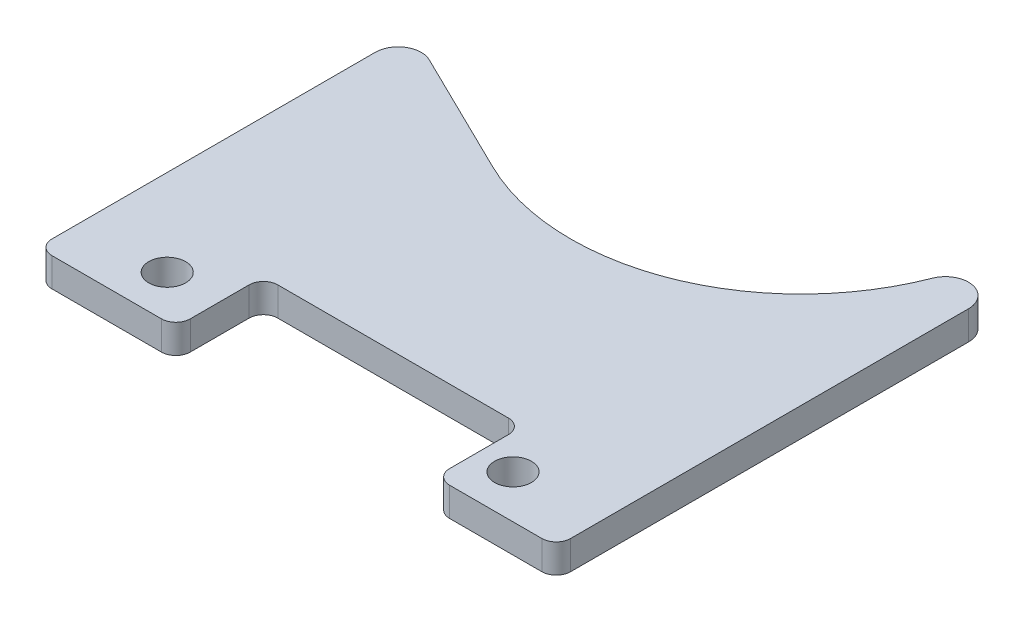
SolidWorks part; units mm, degrees
ref_plane "Front Plane" through (0, 0, 0) normal (0, 0, 1) x (1, 0, 0)
ref_plane "Top Plane" through (0, 0, 0) normal (0, 1, 0) x (1, 0, 0)
ref_plane "Right Plane" through (0, 0, 0) normal (1, 0, 0) x (0, 0, -1)
sketch "Sketch1" plane through (0, 0, 0) normal (0, 1, 0) x (1, 0, 0)
  line L1 (-28.575, 30.1625) -> (28.575, 30.1625)
  line L2 (-28.575, 30.1625) -> (-28.575, -30.1625)
  line L3 (-28.575, -30.1625) -> (28.575, -30.1625)
  line L4 (28.575, 30.1625) -> (28.575, -30.1625)
  line L5 (-28.575, 30.1625) -> (28.575, -30.1625) construction
  line L6 (-28.575, -30.1625) -> (28.575, 30.1625) construction
  point P0 (0, 0)
  dimension "D1" = 57.15
  dimension "D2" = 60.325
extrude "Boss-Extrude1" add sketch "Sketch1" along normal blind 3.175
sketch "Sketch2" plane through (0, 0, 0) normal (0, -1, 0) x (-1, 0, 0)
  line L0 (28.575, -30.1625) -> (-28.575, -30.1625) construction
  line L1 (-19.05, -25.4) -> (-28.575, -25.4) construction
  line L2 (-28.575, -30.1625) -> (-28.575, 30.1625) construction
  line L3 (19.05, -25.4) -> (28.575, -25.4) construction
  line L4 (28.575, 30.1625) -> (28.575, -30.1625) construction
  circle A0 centre (-19.05, -25.4) radius 2.032
  circle A1 centre (19.05, -25.4) radius 2.032
  dimension "D2" = 4.064
  dimension "D1" = 4.7625
  dimension "D3" = 38.1
extrude "Cut-Extrude1" cut sketch "Sketch2" against normal through all
sketch "Sketch3" plane through (0, 3.175, 0) normal (0, 1, 0) x (1, 0, 0)
  line L0 (-28.575, -30.1625) -> (28.575, -30.1625) construction
  line L1 (-13.335, -30.1625) -> (15.24, -30.1625)
  line L2 (-13.335, -30.1625) -> (-13.335, -20.5105)
  line L3 (-13.335, -20.5105) -> (15.24, -20.5105)
  line L4 (15.24, -30.1625) -> (15.24, -20.5105)
  line L5 (-28.575, 30.1625) -> (-28.575, -30.1625) construction
  dimension "D1" = 15.24
  dimension "D2" = 28.575
  dimension "D3" = 9.652
extrude "Cut-Extrude2" cut sketch "Sketch3" against normal through all
fillet "Fillet1" radius 1.5875 6 edges at (-28.575, 1.5875, 30.1625) (-13.335, 1.5875, 30.1625) (-13.335, 1.5875, 20.5105) (15.24, 1.5875, 20.5105) (15.24, 1.5875, 30.1625) (28.575, 1.5875, 30.1625)
sketch "Sketch5" plane through (0, 3.175, 0) normal (0, 1, 0) x (1, 0, 0)
  line L4 (-11.1723, 2.589) -> (-28.575, 11.1125)
  line L5 (-28.575, 30.1625) -> (-28.575, -28.575) construction
  line L6 (23.9755, 17.0135) -> (28.575, 30.1625)
  line L7 (-28.575, 11.1125) -> (-28.575, 30.1625)
  line L8 (-28.575, 30.1625) -> (28.575, 30.1625)
  line L9 (28.575, -28.575) -> (28.575, 30.1625) construction
  line L10 (-26.9875, -30.1625) -> (-14.9225, -30.1625) construction
  arc A1 (-11.1723, 2.589) -> (23.9755, 17.0135) centre (0, 25.4) ccw
  dimension "D1" = 50.8
  dimension "D2" = 25.4
  dimension "D3" = 60.325
  dimension "D4" = 19.05
extrude "Cut-Extrude4" cut sketch "Sketch5" against normal through all
fillet "Fillet2" radius 2.54 2 edges at (28.575, 1.5875, -30.1625) (-28.575, 1.5875, -11.1125)
